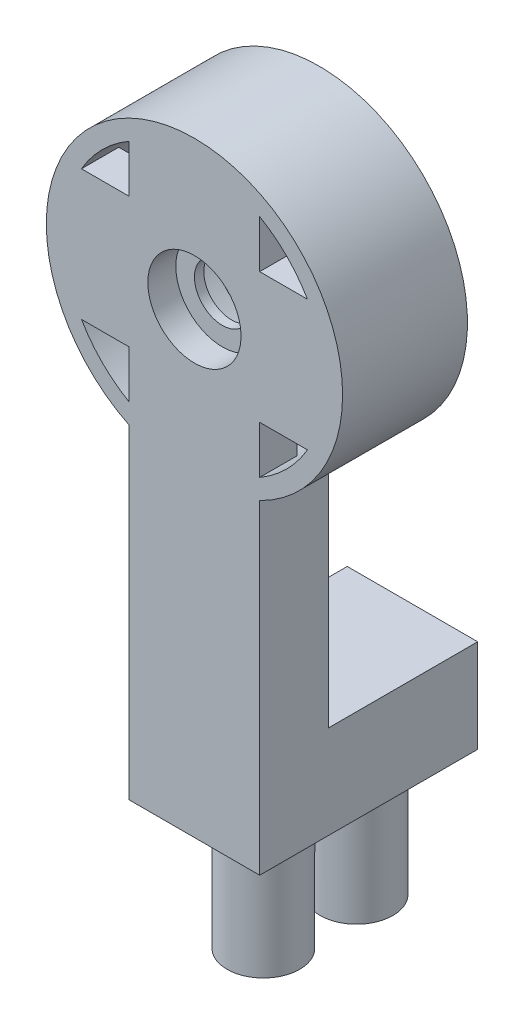
SolidWorks part; units mm, degrees
ref_plane "Front Plane" through (0, 0, 0) normal (0, 0, 1) x (1, 0, 0)
ref_plane "Top Plane" through (0, 0, 0) normal (0, 1, 0) x (1, 0, 0)
ref_plane "Right Plane" through (0, 0, 0) normal (1, 0, 0) x (0, 0, -1)
sketch "Sketch1" plane through (0, 0, 0) normal (0, 0, 1) x (1, 0, 0)
  line L5 (0, -17.5) -> (12.7696, -17.5) construction
  line L26 (0, 0) -> (0, -35) construction
  line L32 (0, 3.5) -> (7.1381, 3.5)
  line L33 (7.1381, 3.5) -> (-7.1381, 3.5)
  line L34 (0, -3.5) -> (7.1381, -3.5)
  line L35 (7.1381, -3.5) -> (-7.1381, -3.5)
  line L36 (3.5, -35) -> (3.5, -41.0622)
  line L37 (-3.5, -35) -> (-3.5, -41.0622)
  line L38 (-3.5, 0) -> (-3.5, 6.0622)
  line L45 (-3.5, 0) -> (-3.5, -35)
  line L47 (3.5, 0) -> (3.5, -35)
  line L48 (3.5, 0) -> (3.5, 6.0622)
  line L49 (7.1381, -31.5) -> (-7.1381, -31.5)
  line L50 (0, -31.5) -> (7.1381, -31.5)
  line L51 (7.1381, -38.5) -> (-7.1381, -38.5)
  line L52 (0, -38.5) -> (7.1381, -38.5)
  circle A0 centre (0, 0) radius 7.95
  circle A1 centre (0, 0) radius 3.5
  circle A2 centre (0, 0) radius 7
  circle A6 centre (0, 0) radius 1.5
  circle A11 centre (0, -35) radius 1.5
  circle A12 centre (0, -35) radius 7
  circle A13 centre (0, -35) radius 3.5
  circle A14 centre (0, -35) radius 7.95
  point P20 (0, -35)
  point P34 (0, -35)
  point P42 (0, 0)
  dimension "D1" = 15.9
  dimension "D2" = 7
  dimension "D6" = 14
  dimension "D9" = 3
  dimension "D3" = 7
  dimension "D7" = 35
extrude "Boss-Extrude4" add sketch "Sketch1" along normal blind 3 contours L48 A2 L38 L33 L32 | A2 L32 A0 L33 | L45 A14 L47 A0 | A14 L51 A12 | A12 L36 L51 L37 | A14 L49 A12 L51 | L36 A13 L51 | L51 A13 L37 | A14 L51 A12 L49 | A13 A11 | L45 A13 L49 | L49 A13 L47 | A12 L45 L49 L47 | A14 L49 A12 L45 | A14 L47 A12 L49 | A14 L45 A12 L47 | A12 L51 L37 L45 L49 | A12 L50 L47 L36 L52 | L45 A2 L47 L34 L35 | A2 L45 A0 L47 | A2 L47 A0 L34 | A2 L34 A0 L32 | A2 L33 A0 L35 | A2 L35 A0 L45 | L33 A2 L35 L45 L38 | L35 A2 L33 L48 L47 | A1 L34 L47 | A1 A6 | A1 L45 L35 | A1 L33 L38 | A1 L48 L32 region at (0, 5.1101, 0) region at (-2.7182, 2.7182, 0) region at (2.7182, 2.7182, 0) region at (2.4049, 2.4049, 0) region at (5.1101, 0, 0) region at (-5.1101, 0, 0) region at (2.7182, -2.7182, 0) region at (-2.7182, -2.7182, 0) region at (5.0555, 5.0555, 0) region at (7.1812, 0, 0) region at (-7.1812, 0, 0) region at (0, -5.1101, 0) region at (-5.2259, -5.2259, 0) region at (5.2259, -5.2259, 0) region at (0, -7.1812, 0) region at (0, -17.5, 0) region at (5.2259, -29.7741, 0) region at (0, -27.8188, 0) region at (-5.2259, -29.7741, 0) region at (0, -29.8899, 0) region at (7.1812, -35, 0) region at (-7.1812, -35, 0) region at (5.1101, -35, 0) region at (2.7182, -32.2818, 0) region at (-2.7182, -32.2818, 0) region at (-5.1101, -35, 0) region at (-6.6001, -38.6495, 0) region at (2.4049, -37.4049, 0) region at (2.7182, -37.7182, 0) region at (-2.7182, -37.7182, 0) region at (0, -40.1101, 0)
sketch "Sketch3" plane through (0, 0, 0) normal (0, 0, -1) x (-1, 0, 0)
  line L0 (-3.5, 6.0622) -> (-3.5, 3.5)
  line L1 (-3.5, 3.5) -> (-6.0622, 3.5)
  line L2 (-3.5, -6.0622) -> (-3.5, -3.5)
  line L3 (-3.5, -3.5) -> (-6.0622, -3.5)
  line L4 (3.5, -6.0622) -> (3.5, -3.5)
  line L5 (3.5, -3.5) -> (6.0622, -3.5)
  line L6 (3.5, 6.0622) -> (3.5, 3.5)
  line L7 (3.5, 3.5) -> (6.0622, 3.5)
  line L8 (0, 0) -> (0, -35) construction
  line L9 (0, -35) -> (0, -17.5) construction
  line L10 (0, -17.5) -> (14.5774, -17.5) construction
  line L11 (-3.5, 3.5) -> (-6.0622, 3.5)
  line L12 (-3.5, 6.0622) -> (-3.5, 3.5)
  line L13 (-3.5, -3.5) -> (-6.0622, -3.5)
  line L14 (-3.5, -6.0622) -> (-3.5, -3.5)
  line L15 (3.5, -3.5) -> (6.0622, -3.5)
  line L16 (3.5, -6.0622) -> (3.5, -3.5)
  line L17 (3.5, 3.5) -> (6.0622, 3.5)
  line L18 (3.5, 6.0622) -> (3.5, 3.5)
  line L19 (3.5, -41.0622) -> (3.5, -38.5)
  line L20 (3.5, -38.5) -> (6.0622, -38.5)
  line L21 (3.5, -28.9378) -> (3.5, -31.5)
  line L22 (3.5, -31.5) -> (6.0622, -31.5)
  line L23 (-3.5, -28.9378) -> (-3.5, -31.5)
  line L24 (-3.5, -31.5) -> (-6.0622, -31.5)
  line L25 (-3.5, -41.0622) -> (-3.5, -38.5)
  line L26 (-3.5, -38.5) -> (-6.0622, -38.5)
  line L27 (3.5, -38.5) -> (6.0622, -38.5)
  line L28 (3.5, -41.0622) -> (3.5, -38.5)
  line L29 (3.5, -31.5) -> (6.0622, -31.5)
  line L30 (3.5, -28.9378) -> (3.5, -31.5)
  line L31 (-3.5, -31.5) -> (-6.0622, -31.5)
  line L32 (-3.5, -28.9378) -> (-3.5, -31.5)
  line L33 (-3.5, -38.5) -> (-6.0622, -38.5)
  line L34 (-3.5, -41.0622) -> (-3.5, -38.5)
  circle A0 centre (0, 0) radius 1.5
  circle A1 centre (0, 0) radius 7.95
  circle A2 centre (0, 0) radius 7
  circle A3 centre (0, -35) radius 7
  circle A4 centre (0, -35) radius 7.95
  circle A5 centre (0, -35) radius 1.5
  line M2 (3.5, -38.5) -> (6.0622, -38.5)
  arc M3 (6.0622, -38.5) -> (3.5, -41.0622) centre (0, -35) cw
  line M4 (3.5, -41.0622) -> (3.5, -38.5)
  line M5 (-3.5, -38.5) -> (-3.5, -41.0622)
  arc M6 (-3.5, -41.0622) -> (-6.0622, -38.5) centre (0, -35) cw
  line M7 (-6.0622, -38.5) -> (-3.5, -38.5)
  arc M9 (3.5, -7.1381) -> (-3.5, -7.1381) centre (0, 0) ccw
  arc M11 (-3.5, -27.8619) -> (3.5, -27.8619) centre (0, -35) ccw
  line M12 (6.0622, -31.5) -> (3.5, -31.5)
  line M13 (3.5, -31.5) -> (3.5, -28.9378)
  arc M14 (3.5, -28.9378) -> (6.0622, -31.5) centre (0, -35) cw
  arc M15 (-3.5, -6.0622) -> (-6.0622, -3.5) centre (0, 0) cw
  line M16 (-6.0622, -3.5) -> (-3.5, -3.5)
  line M17 (-3.5, -3.5) -> (-3.5, -6.0622)
  line M18 (-3.5, -31.5) -> (-6.0622, -31.5)
  arc M19 (-6.0622, -31.5) -> (-3.5, -28.9378) centre (0, -35) cw
  line M20 (-3.5, -28.9378) -> (-3.5, -31.5)
  line M21 (3.5, -3.5) -> (6.0622, -3.5)
  arc M22 (6.0622, -3.5) -> (3.5, -6.0622) centre (0, 0) cw
  line M23 (3.5, -6.0622) -> (3.5, -3.5)
  line M24 (6.0622, 3.5) -> (3.5, 3.5)
  line M25 (3.5, 3.5) -> (3.5, 6.0622)
  arc M26 (3.5, 6.0622) -> (6.0622, 3.5) centre (0, 0) cw
  arc M27 (-6.0622, 3.5) -> (-3.5, 6.0622) centre (0, 0) cw
  line M28 (-3.5, 6.0622) -> (-3.5, 3.5)
  line M29 (-3.5, 3.5) -> (-6.0622, 3.5)
  circle M30 centre (0, 0) radius 1.5
  circle M31 centre (0, -35) radius 1.5
  dimension "D1" = 15.9
extrude "Boss-Extrude5" add sketch "Sketch3" along normal blind 3 contours A1 A2 M9 M26 M22 M15 M27 | A2 M25 M28 M29 M16 M17 M23 M21 M24 M30 | A3 M4 M2 M12 M13 M20 M18 M7 M5 M31 | A4 A3 M11 M3 M6 M19 M14 region at (0, 6.802, 0) region at (0, -41.802, 0) region at (-6.5556, -4.0868, 0) region at (4.0868, -41.5556, 0)
sketch "Sketch4" plane through (0, 0, 3) normal (0, 0, 1) x (1, 0, 0)
  line L0 (0, 0) -> (0, -35) construction
  line L1 (0, -35) -> (0, 0) construction
  line L2 (0, -17.5) -> (19.6941, -17.5) construction
  circle A1 centre (0, -35) radius 2.5
  circle A2 centre (0, 0) radius 2.5
  dimension "D2" = 5
extrude "Cut-Extrude1" cut sketch "Sketch4" against normal blind 1.5
sketch "Sketch5" plane through (0, 0, -3) normal (0, 0, -1) x (-1, 0, 0)
  circle A0 centre (0, 0) radius 7
extrude "Cut-Extrude2" cut sketch "Sketch5" against normal blind 4
sketch "Sketch6" plane through (0, 0, -3) normal (0, 0, -1) x (-1, 0, 0)
  circle A0 centre (0, -35) radius 7.95
extrude "Cut-Extrude3" cut sketch "Sketch6" against normal blind 1
sketch "Sketch7" plane through (0, 0, 1.5) normal (0, 0, 1) x (1, 0, 0)
  circle A0 centre (0, -35) radius 2.5
extrude "Cut-Extrude4" cut sketch "Sketch7" against normal blind 0.5
sketch "Sketch8" plane through (0, 0, -3) normal (0, 0, -1) x (-1, 0, 0)
  circle A0 centre (0, 0) radius 7.95
  circle A1 centre (0, 0) radius 7
extrude "Boss-Extrude6" add sketch "Sketch8" along normal blind 0.7
sketch "Sketch9" plane through (0, 0, -2) normal (0, 0, -1) x (-1, 0, 0)
  line L0 (-3.5, -28.9378) -> (-3.5, -31.5)
  line L1 (-3.5, -31.5) -> (-6.0622, -31.5)
  line L2 (-6.0622, -38.5) -> (-3.5, -38.5)
  line L3 (-3.5, -38.5) -> (-3.5, -41.0622)
  line L4 (6.0622, -38.5) -> (3.5, -38.5)
  line L5 (3.5, -38.5) -> (3.5, -41.0622)
  line L6 (3.5, -28.9378) -> (3.5, -31.5)
  line L7 (3.5, -31.5) -> (6.0622, -31.5)
  circle A0 centre (0, -35) radius 7.95
  circle A1 centre (0, -35) radius 7
  circle A2 centre (0, -35) radius 1.5
  line M1 (6.0622, -31.5) -> (3.5, -31.5)
  line M2 (3.5, -31.5) -> (3.5, -28.9378)
  arc M3 (3.5, -28.9378) -> (6.0622, -31.5) centre (0, -35) cw
  arc M4 (-3.5, -41.0622) -> (-6.0622, -38.5) centre (0, -35) cw
  line M5 (-6.0622, -38.5) -> (-3.5, -38.5)
  line M6 (-3.5, -38.5) -> (-3.5, -41.0622)
  arc M7 (6.0622, -38.5) -> (3.5, -41.0622) centre (0, -35) cw
  line M8 (3.5, -41.0622) -> (3.5, -38.5)
  line M9 (3.5, -38.5) -> (6.0622, -38.5)
  circle M10 centre (0, -35) radius 7.95
  line M11 (-3.5, -31.5) -> (-6.0622, -31.5)
  arc M12 (-6.0622, -31.5) -> (-3.5, -28.9378) centre (0, -35) cw
  line M13 (-3.5, -28.9378) -> (-3.5, -31.5)
  circle M14 centre (0, -35) radius 1.5
extrude "Boss-Extrude8" add sketch "Sketch9" along normal blind 0.7 contours A1 M2 M13 M11 M5 M6 M8 M9 M1 M14 | A1 M10 M3 M7 M4 M12 region at (0, -28.198, -2) region at (7.7251, -35, -2)
sketch "Sketch10" plane through (0, 0, 0) normal (0, 0, -1) x (-1, 0, 0)
  line L2 (-3.5, -7.1381) -> (-3.5, -27.8619)
  line L4 (3.5, -7.1381) -> (3.5, -27.8619)
  circle A0 centre (0, 0) radius 7.95
  circle A1 centre (0, -35) radius 7.95
  line M1 (-3.5, -7.1381) -> (-3.5, -27.8619)
  arc M2 (-3.5, -27.8619) -> (3.5, -27.8619) centre (0, -35) cw
  line M3 (3.5, -27.8619) -> (3.5, -7.1381)
  arc M4 (3.5, -7.1381) -> (-3.5, -7.1381) centre (0, 0) cw
extrude "Boss-Extrude9" add sketch "Sketch10" along normal blind 0.7 contours M4 M1 M2 M3 region at (0, -17.5, 0)
sketch "Sketch15" plane through (0, 0, -2.7) normal (0, 0, -1) x (-1, 0, 0)
  circle A0 centre (0, -35) radius 7
  circle A1 centre (0, -35) radius 4.9497
extrude "Boss-Extrude12" add sketch "Sketch15" against normal blind 5.7
sketch "Sketch16" plane through (0, 0, -2.7) normal (0, 0, -1) x (-1, 0, 0)
  line L1 (-3.5, -31.5) -> (3.5, -31.5)
  line L2 (-3.5, -31.5) -> (-3.5, -38.5)
  line L3 (-3.5, -38.5) -> (3.5, -38.5)
  line L4 (3.5, -31.5) -> (3.5, -38.5)
  line L5 (-3.5, -31.5) -> (3.5, -38.5) construction
  line L6 (-3.5, -38.5) -> (3.5, -31.5) construction
  point P0 (0, -35)
  dimension "D1" = 7
  dimension "D2" = 7
extrude "Cut-Extrude7" cut sketch "Sketch16" against normal blind 5.7
sketch "Sketch17" plane through (0, 0, -2.7) normal (0, 0, -1) x (-1, 0, 0)
  line L0 (0, 0) -> (0, -24.55) construction
  line L2 (-11.0265, -24.55) -> (10.0772, -24.55)
  line L3 (-11.0265, -24.55) -> (-11.0265, -44.0073)
  line L4 (-11.0265, -44.0073) -> (10.0772, -44.0073)
  line L5 (10.0772, -24.55) -> (10.0772, -44.0073)
  dimension "D1" = 24.55
extrude "Cut-Extrude8" cut sketch "Sketch17" against normal blind 10
sketch "Sketch18" plane through (0, -24.55, 0) normal (0, -1, 0) x (1, 0, 0)
  line L0 (0, 3) -> (0, 2.8) construction
  line L1 (3.5, 3) -> (-3.5, 3) construction
  line L2 (0, 2.8) -> (0, -8.7) construction
  line L4 (3.5, -0.7) -> (-3.5, -0.7)
  line L5 (3.5, -0.7) -> (3.5, -8.7)
  line L6 (3.5, -8.7) -> (-3.5, -8.7)
  line L7 (-3.5, -0.7) -> (-3.5, -8.7)
  dimension "D1" = 0.2
  dimension "D2" = 11.5
  dimension "D3" = 8
extrude "Boss-Extrude13" add sketch "Sketch18" against normal blind 5
sketch "Sketch19" plane through (0, -24.55, 0) normal (0, -1, 0) x (1, 0, 0)
  line L0 (0, 3) -> (0, 2.8) construction
  line L1 (-3.5, -8.7) -> (3.5, -8.7) construction
  line L2 (3.5, 3) -> (-3.5, 3) construction
  line L3 (3.5, -8.7) -> (3.5, 3) construction
  circle A0 centre (0, -5.7) radius 1.95
  circle A1 centre (0, -0.7) radius 1.95
  dimension "D2" = 3.9
  dimension "D3" = 3
  dimension "D4" = 3.5
  dimension "D1" = 0.2
  dimension "D5" = 2
extrude "Boss-Extrude14" add sketch "Sketch19" along normal blind 7
